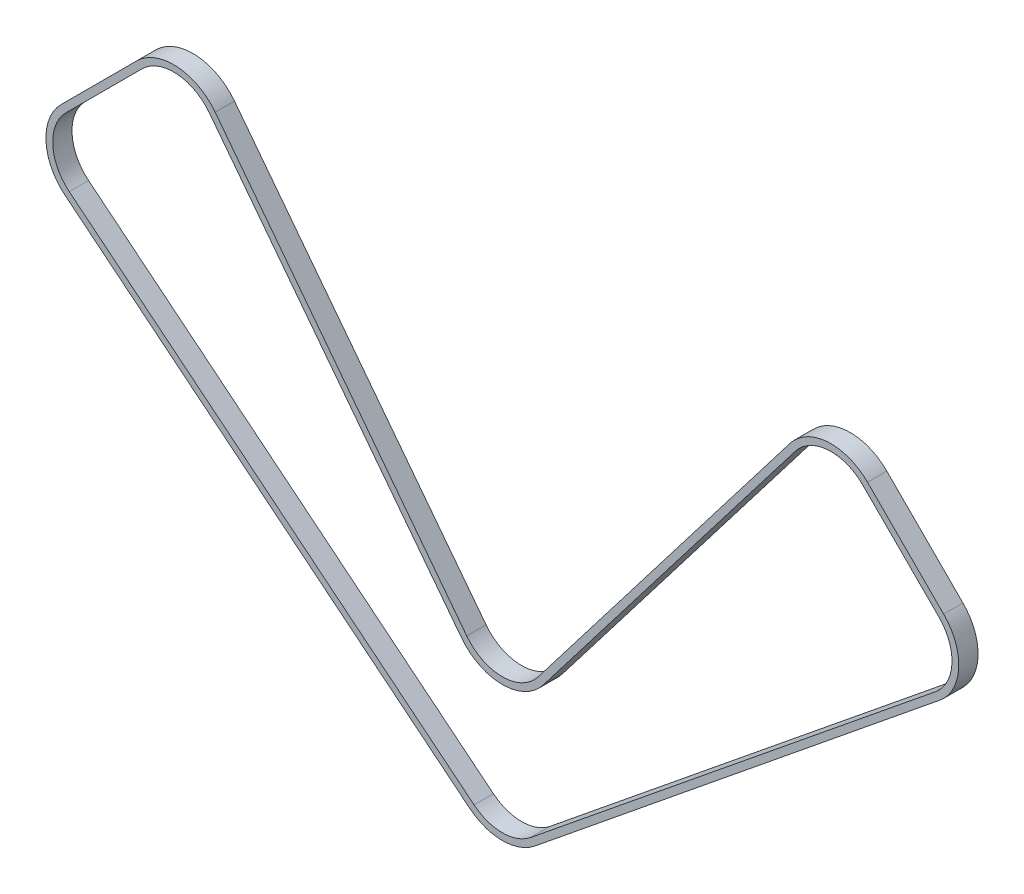
SolidWorks part; units mm, degrees
material "Rubber"
ref_plane "Front Plane" through (0, 0, 0) normal (0, 0, 1) x (1, 0, 0)
ref_plane "Top Plane" through (0, 0, 0) normal (0, 1, 0) x (1, 0, 0)
ref_plane "Right Plane" through (0, 0, 0) normal (1, 0, 0) x (0, 0, -1)
sketch "Sketch2" plane through (0, 0, 0) normal (0, 0, 1) x (1, 0, 0)
  line L0 (0, 0) -> (1, 0) construction
  line L1 (0, 0) -> (0, 1) construction
  line L2 (-16.8605, -20.7674) -> (-226.5696, 149.4894)
  line L3 (-228.6243, 189.172) -> (-189.172, 228.6243)
  line L4 (-148.7731, 225.6468) -> (-21.4838, 54.0623)
  line L5 (21.4838, 54.0623) -> (148.7731, 225.6468)
  line L6 (189.172, 228.6243) -> (228.6243, 189.172)
  line L7 (226.5696, 149.4894) -> (16.8605, -20.7674)
  arc A0 (16.8605, -20.7674) -> (-16.8605, -20.7674) centre (0, 0) cw
  arc A1 (-226.5696, 149.4894) -> (-228.6243, 189.172) centre (-209.7091, 170.2569) cw
  arc A2 (-189.172, 228.6243) -> (-148.7731, 225.6468) centre (-170.2569, 209.7091) cw
  arc A3 (-21.4838, 54.0623) -> (21.4838, 54.0623) centre (0, 70) ccw
  arc A4 (148.7731, 225.6468) -> (189.172, 228.6243) centre (170.2569, 209.7091) cw
  arc A5 (228.6243, 189.172) -> (226.5696, 149.4894) centre (209.7091, 170.2569) cw
sketch "Sketch3" plane through (0, 0, 0) normal (0, 0, 1) x (1, 0, 0)
  line L12 (-148.7731, 225.6468) -> (-18.4409, 55.8455)
  line L13 (-21.4838, 54.0623) -> (-151.8159, 223.8636)
  line L14 (-186.6949, 226.1472) -> (-226.1472, 186.6949)
  line L15 (-189.172, 228.6243) -> (-228.6243, 189.172)
  line L16 (-226.5696, 149.4894) -> (-16.8605, -20.7674)
  line L17 (-224.3616, 152.2091) -> (-14.6525, -18.0478)
  line L18 (14.6525, -18.0478) -> (224.3616, 152.2091)
  line L19 (16.8605, -20.7674) -> (226.5696, 149.4894)
  line L20 (228.6243, 189.172) -> (189.172, 228.6243)
  line L21 (186.6949, 226.1472) -> (226.1472, 186.6949)
  line L22 (18.4409, 55.8455) -> (148.7731, 225.6468)
  line L23 (21.4838, 54.0623) -> (151.8159, 223.8636)
  arc A3 (21.4838, 54.0623) -> (-21.4838, 54.0623) centre (0, 70) cw
  arc A5 (-16.8605, -20.7674) -> (16.8605, -20.7674) centre (0, 0) ccw
  arc A10 (18.4409, 55.8455) -> (-18.4409, 55.8455) centre (0, 70) cw
  arc A12 (-186.6949, 226.1472) -> (-151.8159, 223.8636) centre (-170.2569, 209.7091) cw
  arc A13 (-226.1472, 186.6949) -> (-224.3616, 152.2091) centre (-209.7091, 170.2569) ccw
  arc A14 (151.8159, 223.8636) -> (186.6949, 226.1472) centre (170.2569, 209.7091) cw
  arc A15 (226.1472, 186.6949) -> (224.3616, 152.2091) centre (209.7091, 170.2569) cw
  arc A16 (-148.7731, 225.6468) -> (-189.172, 228.6243) centre (-170.2569, 209.7091) ccw construction
  arc A17 (-228.6243, 189.172) -> (-226.5696, 149.4894) centre (-209.7091, 170.2569) ccw construction
  arc A18 (-148.7731, 225.6468) -> (-189.172, 228.6243) centre (-170.3, 209.1237) ccw
  arc A19 (-228.6243, 189.172) -> (-226.5696, 149.4894) centre (-209.7091, 170.2569) ccw
  arc A20 (-14.6525, -18.0478) -> (14.6525, -18.0478) centre (0, 0) ccw
  arc A21 (-16.8605, -20.7674) -> (16.8605, -20.7674) centre (0, 0) ccw construction
  arc A22 (226.5696, 149.4894) -> (228.6243, 189.172) centre (209.7091, 170.2569) ccw construction
  arc A23 (226.5696, 149.4894) -> (228.6243, 189.172) centre (209.7091, 170.2569) ccw
  arc A24 (189.172, 228.6243) -> (148.7731, 225.6468) centre (170.2569, 209.7091) ccw
  arc A25 (-21.4838, 54.0623) -> (21.4838, 54.0623) centre (0, 70) ccw construction
  dimension "D1" = 3.4995
extrude "Boss-Extrude1" add sketch "Sketch3" along normal blind 5 and the other way blind 5
